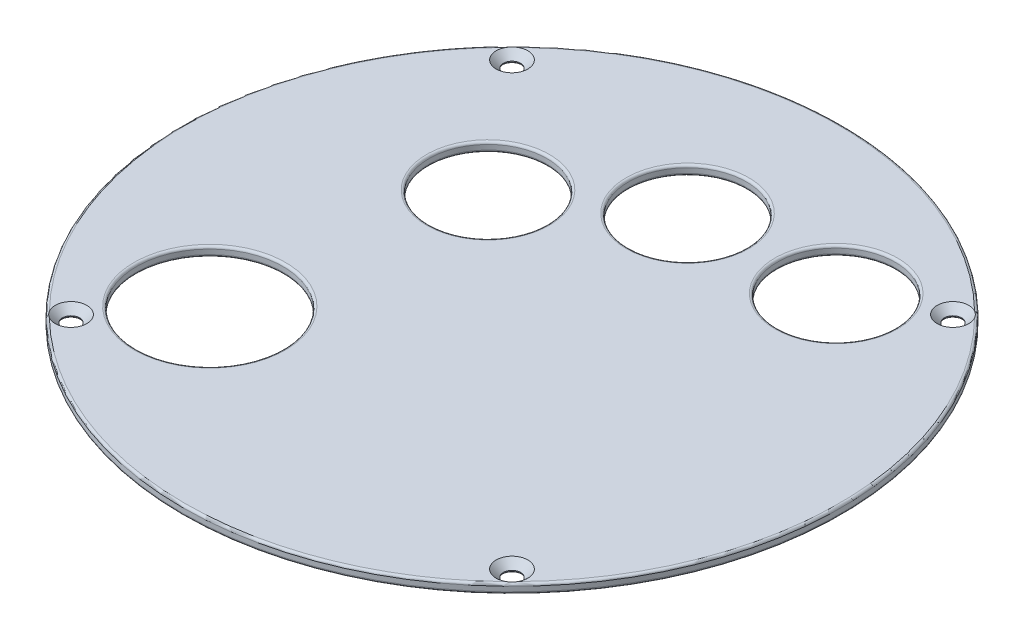
SolidWorks part; units mm, degrees
ref_plane "Front Plane" through (0, 0, 0) normal (0, 0, 1) x (1, 0, 0)
ref_plane "Top Plane" through (0, 0, 0) normal (0, 1, 0) x (1, 0, 0)
ref_plane "Right Plane" through (0, 0, 0) normal (1, 0, 0) x (0, 0, -1)
sketch "Sketch1" plane through (0, 0, 0) normal (0, 1, 0) x (1, 0, 0)
  line L0 (0, 0) -> (-45.9619, 45.9619) construction
  line L5 (-33, -30) -> (-33, 20) construction
  line L6 (-33, 20) -> (-25, 20) construction
  line L7 (0, 0) -> (45.9619, 45.9619) construction
  line L8 (0, 0) -> (45.9619, -45.9619) construction
  line L9 (0, 0) -> (-45.9619, -45.9619) construction
  line L10 (-25, 20) -> (0, 36.5831) construction
  line L11 (0, 36.5831) -> (30, 37.5831) construction
  line L12 (-25, 20) -> (0, 20) construction
  line L13 (0, 20) -> (0, 36.5831) construction
  line L14 (0, 36.5831) -> (30, 36.5831) construction
  line L15 (30, 36.5831) -> (30, 37.5831)
  line L16 (0, 0) -> (0, 20) construction
  line L17 (-45.9619, 45.9619) -> (-43.3103, 43.3103) construction
  line L18 (0, 0) -> (68.7, 0) construction
  circle A0 centre (0, 0) radius 69 construction
  circle A1 centre (0, 0) radius 68.7
  circle A11 centre (-45.9619, 45.9619) radius 1.5 construction
  circle A13 centre (-45.9619, 45.9619) radius 1.8
  circle A14 centre (45.9619, 45.9619) radius 1.8
  circle A15 centre (45.9619, 45.9619) radius 1.5 construction
  circle A16 centre (45.9619, -45.9619) radius 1.8
  circle A17 centre (45.9619, -45.9619) radius 1.5 construction
  circle A18 centre (-45.9619, -45.9619) radius 1.8
  circle A19 centre (-45.9619, -45.9619) radius 1.5 construction
  circle A20 centre (-33, -30) radius 15 construction
  circle A21 centre (-25, 20) radius 12 construction
  circle A22 centre (0, 36.5831) radius 12 construction
  circle A23 centre (30, 37.5831) radius 12 construction
  circle A25 centre (-25, 20) radius 12.3
  circle A26 centre (0, 36.5831) radius 12.3
  circle A27 centre (30, 37.5831) radius 12.3
  circle A28 centre (-33, -30) radius 15.3
  circle A30 centre (30, 37.5831) radius 13 construction
  circle A31 centre (-33, -30) radius 17 construction
  circle A32 centre (0, 0) radius 62.5 construction
  point P40 (0, 0)
  dimension "D1" = 138
  dimension "D5" = 24
  dimension "D7" = 30
  dimension "D9" = 3
  dimension "D6" = 30
  dimension "D17" = 34
  dimension "D18" = 26
  dimension "D19" = 125
  dimension "D20" = 45
  dimension "D3" = 50
  dimension "D4" = 8
  dimension "D8" = 30
  dimension "D11" = 65
  dimension "D13" = 25
  dimension "D14" = 1
  dimension "D15" = 20
  dimension "D2" = 0.3
  dimension "D10" = 0.3
  dimension "D16" = 0.3
  dimension "D12" = 4
extrude "Boss-Extrude1" add sketch "Sketch1" along normal blind 2 contours A1 region at (1.734, 0, 1.7975)
chamfer "Chamfer3" distance 1.5 angle 45 4 edges at (-45.9619, 2, -44.1619) (45.9619, 2, 47.7619) (-45.9619, 2, 47.7619) (45.9619, 2, -44.1619)
fillet "Fillet1" radius 0.5 14 edges at (-45.9619, 0, -44.1619) (45.9619, 0, -44.1619) (45.9619, 0, 47.7619) (-45.9619, 0, 47.7619) (-33, 0, 45.3) (-33, 2, 45.3) (30, 0, -25.2831) (30, 2, -25.2831) (0, 0, -24.2831) (0, 2, -24.2831) (-25, 0, -7.7) (-25, 2, -7.7) (0, 0, 68.7) (0, 2, 68.7)
